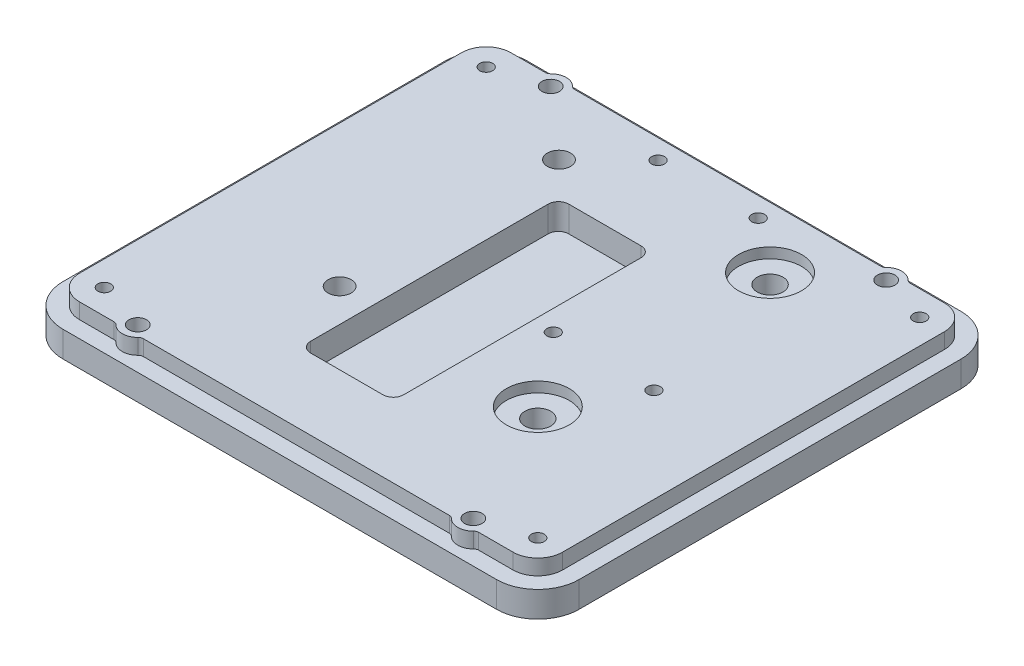
SolidWorks part; units mm, degrees
ref_plane "Front Plane" through (0, 0, 0) normal (0, 0, 1) x (1, 0, 0)
ref_plane "Top Plane" through (0, 0, 0) normal (0, 1, 0) x (1, 0, 0)
ref_plane "Right Plane" through (0, 0, 0) normal (1, 0, 0) x (0, 0, -1)
sketch "Sketch1" plane through (0, 0, 0) normal (0, 1, 0) x (1, 0, 0)
  line L1 (-50, 45) -> (50, 45)
  line L2 (-50, 45) -> (-50, -45)
  line L3 (-50, -45) -> (50, -45)
  line L4 (50, 45) -> (50, -45)
  line L5 (-50, 45) -> (50, -45) construction
  line L6 (-50, -45) -> (50, 45) construction
  point P0 (0, 0)
  dimension "D1" = 100
  dimension "D2" = 90
extrude "Boss-Extrude1" add sketch "Sketch1" along normal blind 8
fillet "Fillet1" radius 8 4 edges at (50, 4, 45) (50, 4, -45) (-50, 4, -45) (-50, 4, 45)
sketch "Sketch6" plane through (0, 8, 0) normal (0, 1, 0) x (1, 0, 0)
  line L0 (20, 30) -> (20, -15) construction
  line L1 (-42, -45) -> (42, -45) construction
  line L2 (50, -37) -> (50, 37) construction
  circle A0 centre (20, 30) radius 6.1
  circle A1 centre (20, -15) radius 6.1
  dimension "D1" = 12.2
  dimension "D2" = 45
  dimension "D3" = 30
  dimension "D4" = 30
extrude "Cut-Extrude1" cut sketch "Sketch6" against normal blind 2
sketch "Sketch7" plane through (0, 8, 0) normal (0, 1, 0) x (1, 0, 0)
  line L4 (-42, -41.8) -> (42, -41.8)
  line L5 (-42, -41.8) -> (42, -41.8)
  line L6 (42, 41.8) -> (-42, 41.8)
  line L7 (42, 41.8) -> (-42, 41.8)
  line L24 (46.8, -37) -> (46.8, 37)
  line L26 (46.8, -37) -> (46.8, 37)
  line L30 (-46.8, 37) -> (-46.8, -37)
  line L31 (-46.8, 37) -> (-46.8, -37)
  arc A8 (42, -41.8) -> (46.8, -37) centre (42, -37) ccw
  arc A20 (42, -41.8) -> (46.8, -37) centre (42, -37) ccw
  arc A24 (46.8, 37) -> (42, 41.8) centre (42, 37) ccw
  arc A26 (46.8, 37) -> (42, 41.8) centre (42, 37) ccw
  arc A28 (-42, 41.8) -> (-46.8, 37) centre (-42, 37) ccw
  arc A29 (-42, 41.8) -> (-46.8, 37) centre (-42, 37) ccw
  arc A30 (-46.8, -37) -> (-42, -41.8) centre (-42, -37) ccw
  arc A31 (-46.8, -37) -> (-42, -41.8) centre (-42, -37) ccw
  dimension "D1" = 3.2
extrude "Cut-Extrude2" cut sketch "Sketch7" against normal blind 3 flip side to cut
hole_wizard "M3x0.5 Tapped Hole1" positions "Sketch8" profile "Sketch9" tap size "M3x0.5" standard "ANSI Metric" end condition through all
sketch "Sketch8" plane through (0, 8, 0) normal (0, 1, 0) x (1, 0, 0)
  line L4 (42, 45) -> (-42, 45) construction
  point P18 (-42, -37)
  point P21 (-42, 37)
  point P24 (42, 37)
  point P27 (42, -37)
  point P30 (-9.7, 38)
  point P33 (9.7, 38)
  point P48 (28.5, -1)
  point P51 (9, -1)
  point P84 (9, -1)
  point P86 (0, 0)
  dimension "D6" = 7
sketch "Sketch9" plane through (-42, 8, 37) normal (1, 0, 0) x (0, 0, 1)
  line L0 (0, 0) -> (0, 8)
  line L1 (0, 8) -> (1.25, 8)
  line L2 (1.25, 8) -> (1.25, 0)
  line L5 (1.25, 0) -> (0, 0)
  line L11 (0, -6.35) -> (0, 107.95) construction
  dimension "Thru Tap Drill Dia." = 2.5
  dimension "Thru Tap Drill Depth" = 8
cosmetic thread "Hole Thread15" parameters "D2"=3
cosmetic thread "Hole Thread18" parameters "D2"=3
cosmetic thread "Hole Thread29" parameters "D2"=3
cosmetic thread "Hole Thread30" parameters "D2"=3
cosmetic thread "Hole Thread36" parameters "D2"=3
cosmetic thread "Hole Thread39" parameters "D2"=3
cosmetic thread "Hole Thread43" parameters "D2"=3
cosmetic thread "Hole Thread44" parameters "D2"=3
hole_wizard "M6x1.0 Tapped Hole2" positions "Sketch10" profile "Sketch11" tap size "M6x1.0" standard "ANSI Metric" end condition through all
sketch "Sketch10" plane through (0, 8, 0) normal (0, 1, 0) x (1, 0, 0)
  point P0 (20, 30)
  point P3 (20, -15)
sketch "Sketch11" plane through (20, 8, -30) normal (1, 0, 0) x (0, 0, 1)
  line L0 (0, 0) -> (0, 8)
  line L1 (0, 8) -> (2.5, 8)
  line L2 (2.5, 8) -> (2.5, 0)
  line L5 (2.5, 0) -> (0, 0)
  line L11 (0, -6.35) -> (0, 107.95) construction
  dimension "Thru Tap Drill Dia." = 5
  dimension "Thru Tap Drill Depth" = 8
cosmetic thread "Hole Thread11" parameters "D2"=6
cosmetic thread "Hole Thread12" parameters "D2"=6
sketch "Sketch12" plane through (0, 8, 0) normal (0, 1, 0) x (1, 0, 0)
  line L0 (-32.5, 40) -> (32.5, 40) construction
  line L1 (32.5, 40) -> (32.5, -40) construction
  line L2 (32.5, -40) -> (-32.5, -40) construction
  line L3 (-32.5, -40) -> (-32.5, 40) construction
  line L4 (42, 45) -> (-42, 45) construction
  line L5 (-42, -45) -> (42, -45) construction
  line L6 (-50, 37) -> (-50, -37) construction
  line L7 (50, -37) -> (50, 37) construction
  circle A0 centre (-32.5, 40) radius 1.6608
  circle A1 centre (-32.5, 40) radius 3
  circle A3 centre (32.5, 40) radius 3
  circle A5 centre (-32.5, -40) radius 3
  circle A7 centre (32.5, -40) radius 3
  circle A8 centre (32.5, 40) radius 1.6608
  circle A9 centre (32.5, -40) radius 1.6608
  circle A10 centre (-32.5, -40) radius 1.6608
  dimension "D1" = 6
  dimension "D2" = 5
  dimension "D3" = 5
  dimension "D4" = 17.5
  dimension "D5" = 17.5
extrude "Boss-Extrude2" add sketch "Sketch12" against normal up to surface (3 mm away) up to face at (0, 5, 0)
hole_wizard "CBORE for M3 SHCS1" positions "Sketch13" profile "Sketch14" counterbore size "M3" standard "ANSI Metric" end condition through all
sketch "Sketch13" plane through (0, 0, 0) normal (0, -1, 0) x (-1, 0, 0)
  line L0 (-20, 30) -> (-20, -15) construction
  line L2 (-20, 7.5) -> (-77.5775, 7.5) construction
  point P0 (32.5, -40)
  point P3 (-32.5, -40)
  point P6 (32.5, 40)
  point P9 (-32.5, 40)
sketch "Sketch14" plane through (-32.5, 0, 40) normal (1, 0, 0) x (0, 0, -1)
  line L0 (0, 0) -> (0, 8)
  line L1 (0, 8) -> (1.7, 8)
  line L3 (1.7, 8) -> (1.7, 3)
  line L4 (1.7, 3) -> (3.25, 3)
  line L5 (3.25, 3) -> (3.25, 0)
  line L7 (3.25, 0) -> (0, 0)
  line L11 (0, -6.35) -> (0, 107.95) construction
  dimension "Thru Hole Dia." = 3.4
  dimension "Thru Hole Depth" = 8
  dimension "C'Bore Dia." = 6.5
  dimension "C'Bore Depth" = 3
fillet "Fillet2" radius 1 8 edges at (-30.1, 6.5, -41.8) (-34.9, 6.5, -41.8) (34.9, 6.5, -41.8) (30.1, 6.5, -41.8) (34.9, 6.5, 41.8) (30.1, 6.5, 41.8) (-30.1, 6.5, 41.8) (-34.9, 6.5, 41.8)
sketch "Sketch15" plane through (0, 8, 0) normal (0, 1, 0) x (1, 0, 0)
  line L1 (-13, 22) -> (5, 22)
  line L2 (-13, 22) -> (-13, -28)
  line L3 (-13, -28) -> (5, -28)
  line L4 (5, 22) -> (5, -28)
  line L5 (-50, 37) -> (-50, -37) construction
  line L6 (-42, -45) -> (42, -45) construction
  dimension "D1" = 18
  dimension "D2" = 50
  dimension "D3" = 17
  dimension "D4" = 37
extrude "Cut-Extrude3" cut sketch "Sketch15" against normal blind 5
fillet "Fillet3" radius 2 4 edges at (-13, 5.5, 28) (5, 5.5, 28) (5, 5.5, -22) (-13, 5.5, -22)
hole_wizard "CBORE for M4 SHCS1" positions "Sketch16" profile "Sketch17" counterbore size "M4" standard "ANSI Metric" end condition through all
sketch "Sketch16" plane through (0, 0, 0) normal (0, -1, 0) x (-1, 0, 0)
  point P0 (19.4, -14)
  point P3 (19.4, 28.5)
sketch "Sketch17" plane through (-19.4, 0, 14) normal (1, 0, 0) x (0, 0, -1)
  line L0 (0, 0) -> (0, 8)
  line L1 (0, 8) -> (2.25, 8)
  line L3 (2.25, 8) -> (2.25, 4)
  line L4 (2.25, 4) -> (4, 4)
  line L5 (4, 4) -> (4, 0)
  line L7 (4, 0) -> (0, 0)
  line L11 (0, -6.35) -> (0, 107.95) construction
  dimension "Thru Hole Dia." = 4.5
  dimension "Thru Hole Depth" = 8
  dimension "C'Bore Dia." = 8
  dimension "C'Bore Depth" = 4
